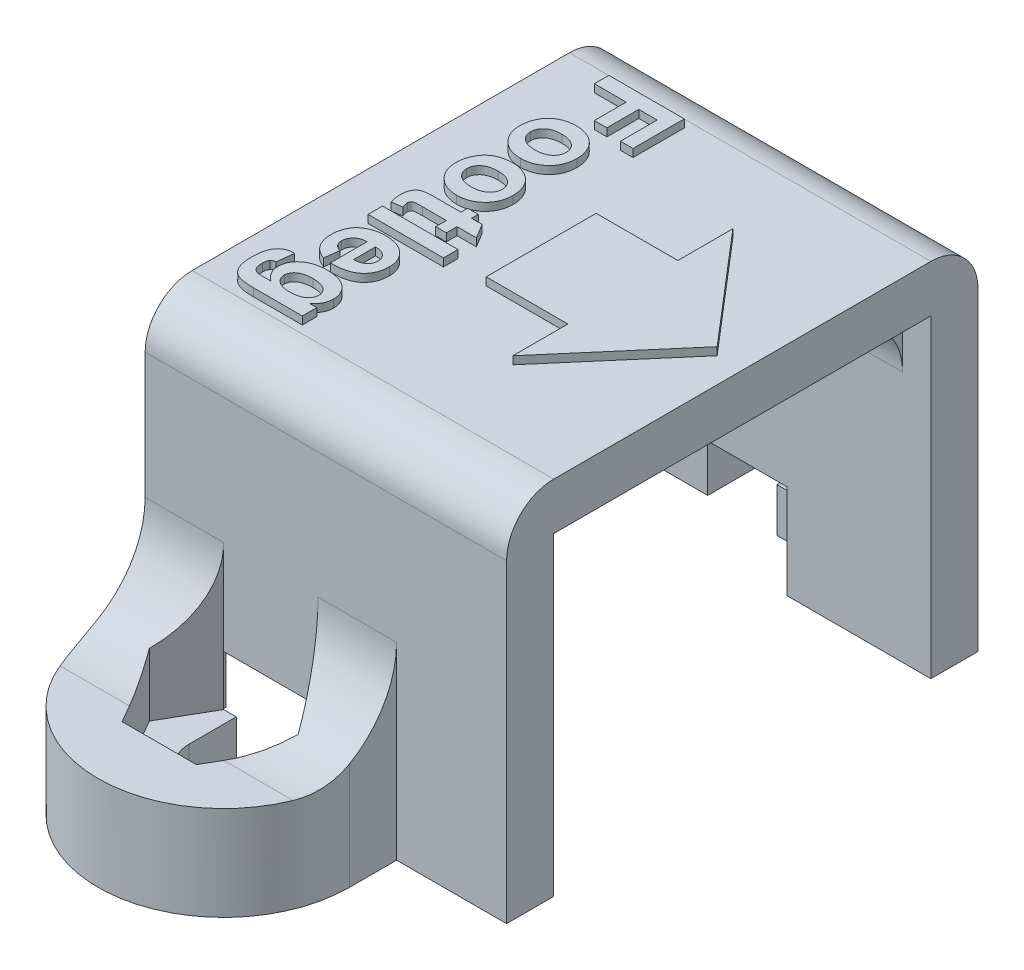
SolidWorks part; units mm, degrees
material "Custom Plastic"
ref_plane "Front Plane" through (0, 0, 0) normal (0, 0, 1) x (1, 0, 0)
ref_plane "Top Plane" through (0, 0, 0) normal (0, 1, 0) x (1, 0, 0)
ref_plane "Right Plane" through (0, 0, 0) normal (1, 0, 0) x (0, 0, -1)
sketch "Sketch38" plane through (0, 0, 0) normal (0, 1, 0) x (1, 0, 0)
  line L0 (0, 9) -> (0, -9) construction
  line L1 (4, 9) -> (4, -9)
  line L2 (-4, 9) -> (-4, -9)
  line L3 (-4.4, 0) -> (4.4, 0) construction
  line L4 (0, -14.3) -> (0, 14.3) construction
  arc A0 (4, 9) -> (-4, 9) centre (0, 9) ccw
  arc A1 (-4, -9) -> (4, -9) centre (0, -9) ccw
  point P3 (0, 13)
  point P4 (0, 0)
  point P9 (0, -13)
  dimension "D1" = 26
  dimension "D3" = 4
  dimension "D2" = 18
extrude "Boss-Extrude_BaseFoot" add sketch "Sketch38" along normal blind 3 separate body
sketch "Sketch1" plane through (4, 0, 0) normal (1, 0, 0) x (0, 0, 1)
  line L0 (9, -3) -> (-9, -3) construction
  line L1 (9, 0) -> (-9, 0) construction
  line L4 (-9, -3) -> (9, -3) construction
  line L9 (-9, 0) -> (9, 0) construction
  line L10 (7.5, -3) -> (-7.5, -3)
  line L11 (7.5, -3) -> (7.5, 0)
  line L12 (7.5, 0) -> (-7.5, 0)
  line L13 (-7.5, -3) -> (-7.5, 0)
  point P11 (0, -3)
  point P12 (0, -3)
  dimension "D1" = 15
extrude "Boss-Extrude_ExtendBase" add sketch "Sketch1" along normal blind 3.5
sketch "Sketch4" plane through (0, 3, 0) normal (0, 1, 0) x (-1, 0, 0)
  line L7 (-1.1836, -11.05) -> (1.1836, -11.05)
  line L8 (1.1836, -11.05) -> (2.3671, -9)
  line L9 (2.3671, -9) -> (1.1836, -6.95)
  line L10 (1.1836, -6.95) -> (-1.1836, -6.95)
  line L11 (-1.1836, -6.95) -> (-2.3671, -9)
  line L12 (-2.3671, -9) -> (-1.1836, -11.05)
  circle A0 centre (0, -9) radius 2.05 construction
  dimension "D1" = 4.1
extrude "Cut-Extrude_HexHole" cut sketch "Sketch4" against normal blind 1.6
sketch "Sketch12" plane through (0, 1.4, 0) normal (0, 1, 0) x (-1, 0, 0)
  line L0 (-1.1, -7.5) -> (-1.1, -9)
  line L1 (1.1, -9) -> (1.1, -7.5)
  line L2 (1.1, -7.5) -> (-1.1, -7.5)
  arc A0 (1.1, -9) -> (-1.1, -9) centre (0, -9) cw
  dimension "D1" = 2.2
  dimension "D2" = 1.5
extrude "Cut-Extrude_BoltHole" cut sketch "Sketch12" against normal through all
mirror "Mirror_BoltNutHole" about plane through (0, 0, 0) normal (0, 0, 1) of "Cut-Extrude_BoltHole", "Cut-Extrude_HexHole"
sketch "Sketch6" plane through (0, 0, 0) normal (0, 1, 0) x (-1, 0, 0)
  line L0 (4, -9) -> (4, 9) construction
  line L1 (-7.5, 7.5) -> (4, 7.5)
  line L2 (-7.5, 7.5) -> (-7.5, -7.5)
  line L3 (-7.5, -7.5) -> (4, -7.5)
  line L4 (4, 7.5) -> (4, -7.5)
  line L9 (-7.5, -7.5) -> (-4, -7.5) construction
extrude "Boss-Extrude_MainBody" add sketch "Sketch6" along normal blind 11.5
fillet "Fillet4" radius 3 4 edges at (2.7506, 3, 7.5) (-2.7506, 3, 7.5) (-2.7506, 3, -7.5) (2.7506, 3, -7.5)
sketch "Sketch2" plane through (0, 0, 0) normal (0, -1, 0) x (1, 0, 0)
  line L0 (0, -9) -> (0, 9) construction
  line L1 (-2.9284, 7.5) -> (2.9284, 7.5)
  line L3 (-2.9284, 7.5) -> (-2.9284, -7.5)
  line L4 (7.5, -7.5) -> (4, -7.5) construction
  line L8 (-2.9284, -7.5) -> (2.9284, -7.5)
  line L9 (2.9284, 7.5) -> (2.9284, -7.5)
  line L10 (7.5, 7.5) -> (4, 7.5) construction
  line L11 (7.5, -7.5) -> (-4, -7.5) construction
  line L12 (-1.5011, -7.5) -> (-1.1, -7.5) construction
  point P6 (0, -7.5)
extrude "Cut-Extrude_BaseNutsHole" cut sketch "Sketch2" against normal blind 3
sketch "Sketch40" plane through (-4, 0, 0) normal (-1, 0, 0) x (0, 0, 1)
  line L0 (-9, 0) -> (9, 0) construction
  line L1 (-6, 10) -> (6, 10)
  line L2 (-6, 10) -> (-6, 0)
  line L3 (-6, 0) -> (6, 0)
  line L4 (6, 10) -> (6, 0)
  line L8 (-9, 0) -> (9, 0) construction
  point P9 (0, 0)
  point P10 (0, 0)
  dimension "D1" = 12
  dimension "D2" = 10
extrude "Cut-Extrude_MotorGearbox" cut sketch "Sketch40" against normal through all
sketch "Sketch Text Line" plane through (0, 11.5, 0) normal (0, 1, 0) x (1, 0, 0)
  line L0 (-2.5, 7.5) -> (-2.5, -7.5)
  line L1 (-4, 7.5) -> (-4, -7.5) construction
  line L2 (7.5, 7.5) -> (-4, 7.5) construction
  line L3 (-4, -7.5) -> (7.5, -7.5) construction
  dimension "D1" = 1.5
sketch "Sketch37" plane through (0, 11.5, 0) normal (0, 1, 0) x (-1, 0, 0)
  line L0 (6.325, 0) -> (-6.325, 0) construction
  line L1 (2.5, -7.5) -> (2.5, 7.5) construction
  line L2 (-6.7, 0) -> (-3.7, 3.5)
  line L3 (-3.7, 3.5) -> (-3.7, 1.75)
  line L4 (-3.7, 1.75) -> (-1.1, 1.75)
  line L5 (-1.1, 1.75) -> (-1.1, -1.75)
  line L6 (-1.1, -1.75) -> (-3.7, -1.75)
  line L7 (-3.7, -1.75) -> (-3.7, -3.5)
  line L8 (-3.7, -3.5) -> (-6.7, 0)
  line L9 (-7.5, 7.5) -> (-7.5, -7.5) construction
  text T0 "Footleg" font "Arial" height 2.4
  point P11 (-7.5, 0)
  dimension "D1" = 3.8
  dimension "D2" = 3.5
  dimension "D3" = 3.5
  dimension "D4" = 1.75
  dimension "D5" = 1.75
  dimension "D6" = 0.8
  dimension "D7" = 2.6
  dimension "D8" = 2.5
extrude "Boss-Extrude_Logo" add sketch "Sketch37" along normal blind 0.25
fillet "Fillet3" radius 1.5 2 edges at (1.75, 11.5, -7.5) (1.75, 11.5, 7.5)
fillet "Fillet5" radius 2 2 edges at (1.75, 10, 6) (1.75, 10, -6)
ref_plane "Plane2" through (7.6, 0, 0) normal (1, 0, 0) x (0, 0, -1)
sketch "Sketch44" plane through (7.6, 0, 0) normal (1, 0, 0) x (0, 0, -1)
  line L5 (6, 8) -> (6, 0) construction
  line L6 (6, 0) -> (-6, 0)
  line L7 (6, 0) -> (6, 10)
  line L8 (6, 10) -> (-6, 10)
  line L9 (-6, 0) -> (-6, 10)
  line L10 (-6, 0) -> (-6, 8) construction
  line L11 (-4, 10) -> (4, 10) construction
  line L12 (9, 0) -> (-9, 0) construction
extrude "Cut-Extrude Notch1" cut sketch "Sketch44" against normal blind 1
pattern_linear "LPattern1" count 2 spacing 5 along (-1, 0, 0) of "Cut-Extrude Notch1"
pattern_linear "LPattern2" count 2 spacing 8.2 along (-1, 0, 0) of "Cut-Extrude Notch1"
